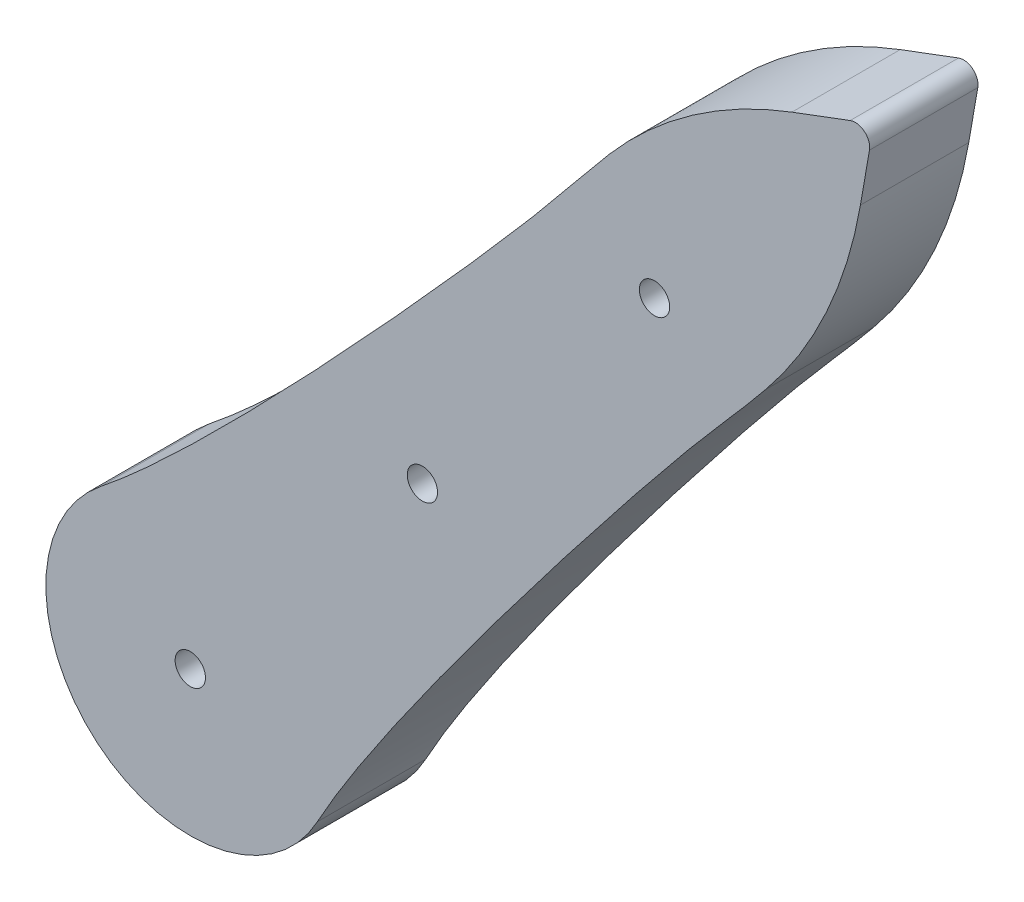
SolidWorks part; units mm, degrees
material "ABS"
ref_plane "Front Plane" through (0, 0, 0) normal (0, 0, 1) x (1, 0, 0)
ref_plane "Top Plane" through (0, 0, 0) normal (0, 1, 0) x (1, 0, 0)
ref_plane "Right Plane" through (0, 0, 0) normal (1, 0, 0) x (0, 0, -1)
sketch "Sketch3" plane through (0, 0, 16) normal (0, 0, 1) x (1, 0, 0)
  line L0 (141.7182, -118.9157) -> (13.1607, -272.1246) construction
  line L2 (135.2182, -125.4157) -> (148.2182, -125.4157) construction
  line L3 (135.2182, -125.4157) -> (135.2182, -112.4157) construction
  line L4 (135.2182, -112.4157) -> (148.2182, -112.4157) construction
  line L5 (148.2182, -125.4157) -> (148.2182, -112.4157) construction
  line L6 (135.2182, -125.4157) -> (148.2182, -112.4157) construction
  line L7 (135.2182, -112.4157) -> (148.2182, -125.4157) construction
  arc A0 (155.0191, -142.9851) -> (115.7048, -109.9965) centre (141.7182, -118.9157) ccw
  circle A1 centre (109.5788, -157.2179) radius 1.6 construction
  circle A2 centre (135.2182, -112.4157) radius 1.6
  arc A3 (0.7245, -256.4612) -> (30.7456, -281.652) centre (13.1607, -272.1246) ccw
  circle A4 centre (148.2182, -112.4157) radius 1.6
  circle A5 centre (148.2182, -125.4157) radius 1.6
  circle A6 centre (135.2182, -125.4157) radius 1.6
  circle A7 centre (77.4395, -195.5202) radius 1.6
  circle A8 centre (45.3001, -233.8224) radius 1.6
  circle A9 centre (13.1607, -272.1246) radius 1.6
  spline S0 degree 3 poles (115.7048, -109.9965) (101.9488, -150.1167) (78.1788, -171.7728) (58.7171, -197.0824) (16.357, -244.0495) (0.7245, -256.4612) knots 0 0 0 0 0.61909 0.71909 1 1 1 1
  spline S1 degree 3 poles (155.0191, -142.9851) (117.8971, -163.4989) (100.6976, -190.6684) (79.1521, -214.2294) (40.2542, -264.1017) (30.7456, -281.652) knots 0 0 0 0 0.61909 0.71909 1 1 1 1
extrude "Boss-Extrude1" add sketch "Sketch3" along normal blind 15
sketch "Sketch4" plane through (0, 0, 31) normal (0, 0, 1) x (1, 0, 0)
  line L1 (81.6816, -169.2386) -> (116.9009, -107.0687)
  line L5 (103.1733, -186.0751) -> (159.1617, -140.1754)
  line L6 (81.6816, -169.2386) -> (107.8011, -159.4411)
  line L7 (103.1733, -186.0751) -> (107.8011, -159.4411)
  arc A0 (159.1442, -140.1897) -> (116.9009, -107.0687) centre (141.7182, -118.9157) ccw
  arc A1 (159.1442, -140.1897) -> (116.9009, -107.0687) centre (141.7182, -118.9157) ccw
  spline S0 degree 3 poles (115.7048, -109.9965) (101.9488, -150.1167) (78.1788, -171.7728) (58.7171, -197.0824) (16.357, -244.0495) (0.7245, -256.4612) knots 0 0 0 0 0.61909 0.71909 1 1 1 1 construction
  spline S1 degree 3 poles (30.7456, -281.652) (40.2542, -264.1017) (79.1521, -214.2294) (100.6976, -190.6684) (117.8971, -163.4989) (155.0191, -142.9851) knots 0 0 0 0 0.28091 0.38091 1 1 1 1 construction
  circle M4 centre (148.2182, -125.4157) radius 1.6
  circle M5 centre (148.2182, -112.4157) radius 1.6
  spline M6 degree 3 poles (115.7048, -109.9965) (101.9488, -150.1167) (78.1788, -171.7728) (58.7171, -197.0824) (16.357, -244.0495) (0.7245, -256.4612) knots 0 0 0 0 0.61909 0.71909 1 1 1 1
  arc M9 (155.0191, -142.9851) -> (115.7048, -109.9965) centre (141.7182, -118.9157) ccw
  circle M10 centre (135.2182, -112.4157) radius 1.6
  circle M11 centre (135.2182, -125.4157) radius 1.6
  dimension "D1" = 55
extrude "Cut-Extrude1" cut sketch "Sketch4" against normal blind 15 contours M9 M6 M5 M10 M11 M4 region at (131.461, -132.3441, 31) body kept at (30.7456, -281.652, 16)
fillet "Fillet3" radius 62 2 edges at (81.6816, -169.2386, 23.5) (103.1733, -186.0751, 23.5)
sketch "Sketch5" plane through (0, 0, 31) normal (0, 0, 1) x (1, 0, 0)
  circle A1 centre (77.4395, -195.5202) radius 2.1
  circle A2 centre (45.3001, -233.8224) radius 2.1
  circle A3 centre (13.1607, -272.1246) radius 2.1
  dimension "D1" = 4.2
  dimension "D2" = 4.2
  dimension "D3" = 4.2
extrude "Cut-Extrude2" cut sketch "Sketch5" against normal blind 15
fillet "Fillet4" radius 2 1 edges at (107.8011, -159.4411, 23.5)
equation "\"thighLength\"=185"
equation "\"legLength\"=200"
equation "\"m3Thru\"=3.2"
equation "\"m4Thru\"=4.3"
equation "\"m3Insert\"=4.2"
equation "\"m4Insert\"=5.3"
equation "\"shoulder5mm\"=5.1"
equation "\"6706out\"=37.125"
equation "\"6706in\"=30"
equation "\"6904out\"=30.125"
equation "\"6904in\"=17"
equation "\"D1@Sketch5\"=\"m3Insert\" "
equation "\"D2@Sketch5\"=\"m3Insert\" "
equation "\"D3@Sketch5\"=\"m3Insert\" "
